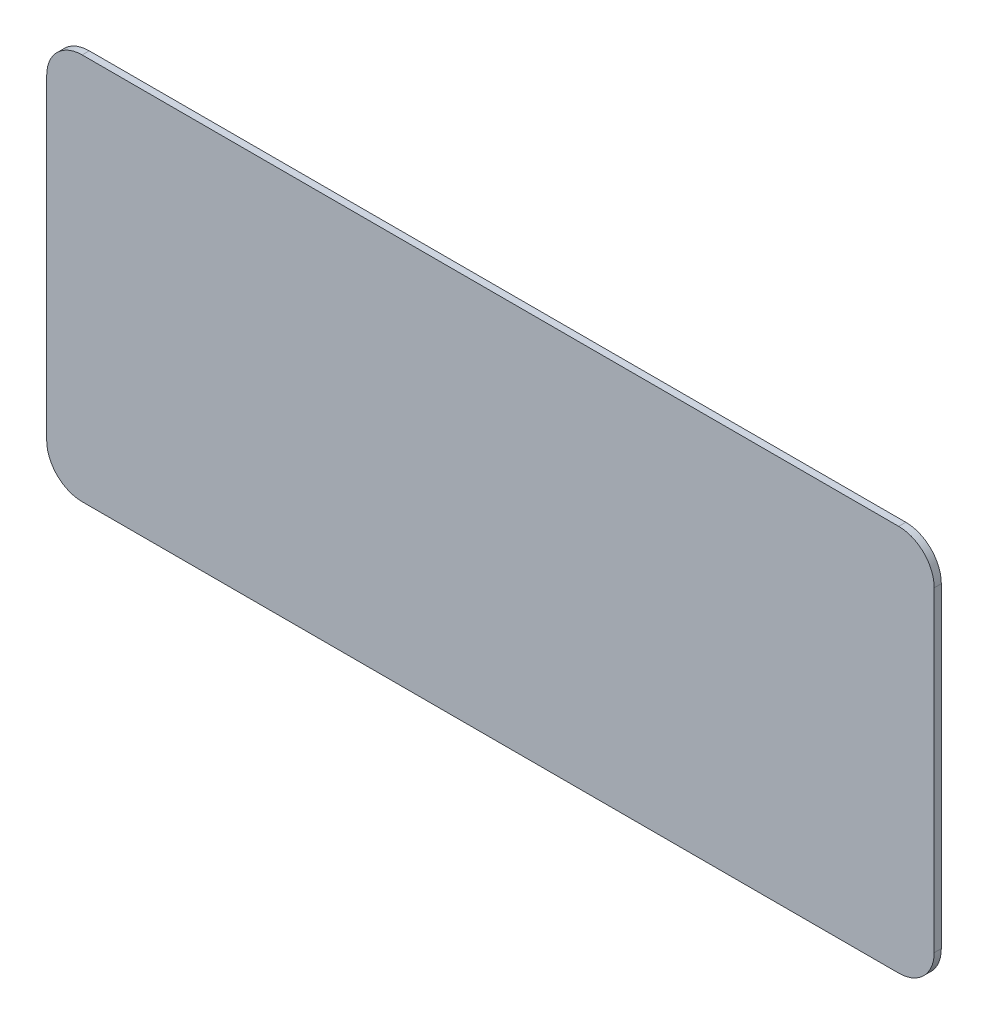
SolidWorks part; units mm, degrees
material "Acrylic (Medium-high impact)"
ref_plane "Front Plane" through (0, 0, 0) normal (0, 0, 1) x (1, 0, 0)
ref_plane "Top Plane" through (0, 0, 0) normal (0, 1, 0) x (1, 0, 0)
ref_plane "Right Plane" through (0, 0, 0) normal (1, 0, 0) x (0, 0, -1)
sketch "Sketch1" plane through (0, 0, 0) normal (0, 0, 1) x (1, 0, 0)
  line L1 (-245, -104) -> (245, -104) construction
  line L2 (-245, -104) -> (-245, 104) construction
  line L3 (-245, 104) -> (245, 104) construction
  line L4 (245, -104) -> (245, 104) construction
  line L5 (-245, -104) -> (245, 104) construction
  line L6 (-245, 104) -> (245, -104) construction
  line L7 (-250, -109) -> (250, -109)
  line L8 (-250, -109) -> (-250, 109)
  line L9 (-250, 109) -> (250, 109)
  line L10 (250, -109) -> (250, 109)
  line L11 (-250, -109) -> (250, 109) construction
  line L12 (-250, 109) -> (250, -109) construction
  point P0 (0, 0)
  dimension "D1" = 490
  dimension "D2" = 208
  dimension "D3" = 5
  dimension "D4" = 5
extrude "Boss-Extrude1" add sketch "Sketch1" along normal blind 4
fillet "Fillet1" radius 20 4 edges at (-250, -109, 2) (-250, 109, 2) (250, 109, 2) (250, -109, 2)
